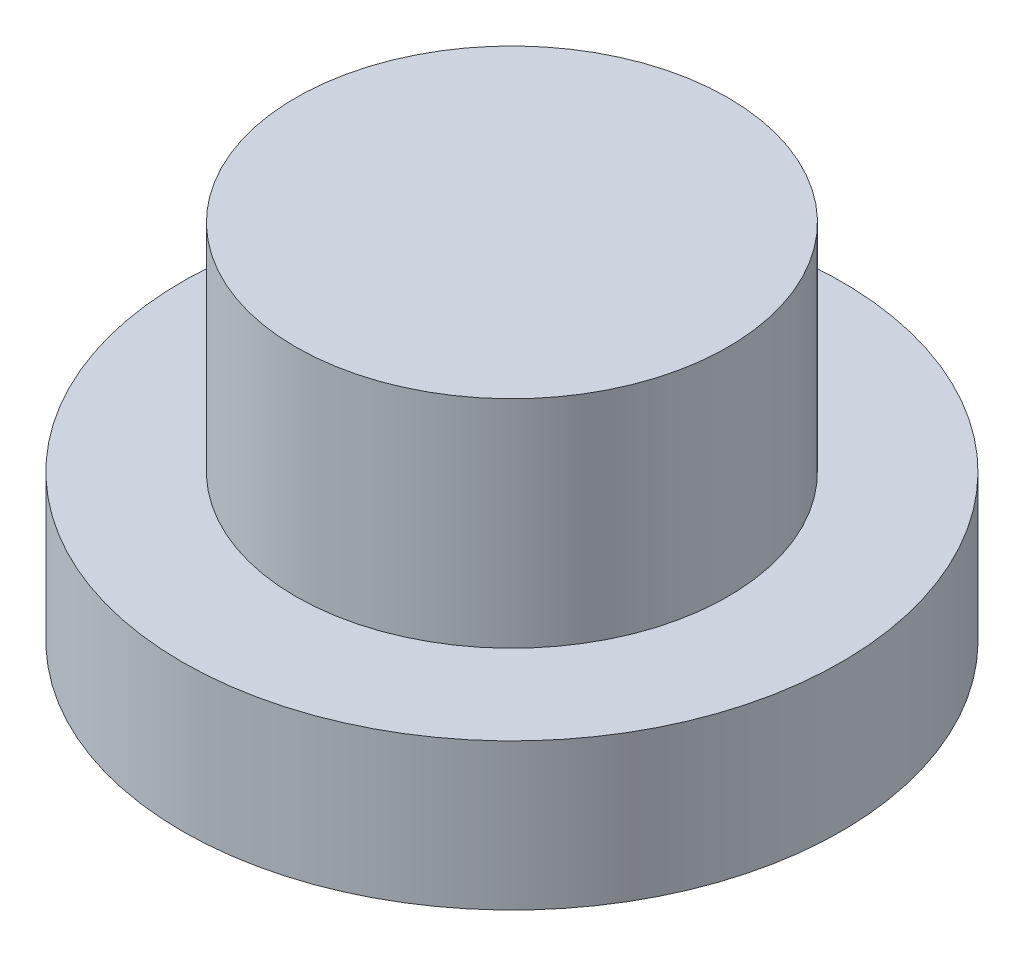
SolidWorks part; units mm, degrees
material "PTFE (general)"
ref_plane "Front Plane" through (0, 0, 0) normal (0, 0, 1) x (1, 0, 0)
ref_plane "Top Plane" through (0, 0, 0) normal (0, 1, 0) x (1, 0, 0)
ref_plane "Right Plane" through (0, 0, 0) normal (1, 0, 0) x (0, 0, -1)
sketch "Sketch1" plane through (0, 0, 0) normal (0, 1, 0) x (1, 0, 0)
  circle A0 centre (0, 0) radius 9
  dimension "D1" = 18
extrude "Boss-Extrude1" add sketch "Sketch1" along normal blind 4
sketch "Sketch2" plane through (0, 4, 0) normal (0, 1, 0) x (1, 0, 0)
  circle A0 centre (0, 0) radius 5.9
  dimension "D1" = 11.8
extrude "Boss-Extrude2" add sketch "Sketch2" along normal blind 20
sketch "Sketch5" plane through (0, 24, 0) normal (0, 1, 0) x (1, 0, 0)
  circle A0 centre (0, 0) radius 9.8378
extrude "Cut-Extrude3" cut sketch "Sketch5" against normal offset from surface (14.1 mm away) 5.9 up to face at (0, 4, 5.9)
